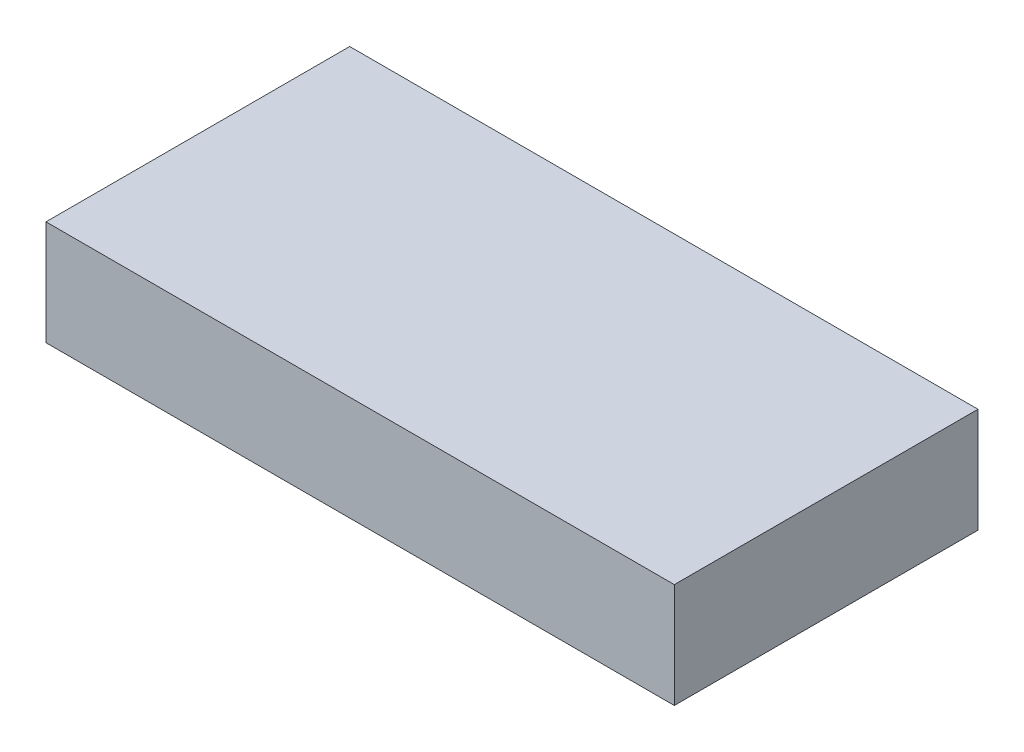
SolidWorks part; units mm, degrees
ref_plane "Front Plane" through (0, 0, 0) normal (0, 0, 1) x (1, 0, 0)
ref_plane "Top Plane" through (0, 0, 0) normal (0, 1, 0) x (1, 0, 0)
ref_plane "Right Plane" through (0, 0, 0) normal (1, 0, 0) x (0, 0, -1)
sketch "Sketch1" plane through (0, 0, 0) normal (0, 1, 0) x (1, 0, 0)
  line L1 (0, 0) -> (30, 0)
  line L2 (0, 0) -> (0, 14.5)
  line L3 (0, 14.5) -> (30, 14.5)
  line L4 (30, 0) -> (30, 14.5)
  point P4 (0, 0)
  dimension "D1" = 30
  dimension "D2" = 14.5
extrude "Boss-Extrude1" add sketch "Sketch1" along normal blind 5
